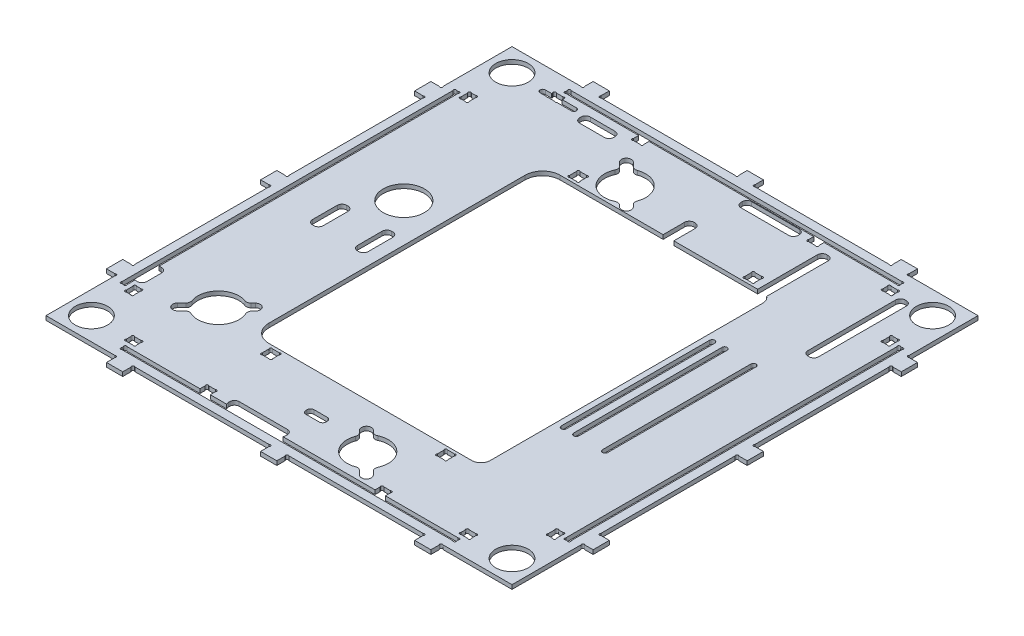
SolidWorks part; units mm, degrees
ref_plane "Front Plane" through (0, 0, 0) normal (0, 0, 1) x (1, 0, 0)
ref_plane "Top Plane" through (0, 0, 0) normal (0, 1, 0) x (1, 0, 0)
ref_plane "Right Plane" through (0, 0, 0) normal (1, 0, 0) x (0, 0, -1)
sketch "Sketch3" plane through (0, 0, 0) normal (0, 1, 0) x (1, 0, 0)
  line L0 (24.2967, 388.9163) -> (24.2967, 184.8114)
  line L1 (25.4192, 183.6889) -> (26.3491, 183.6889)
  line L2 (27.4717, 184.8114) -> (27.4717, 388.9163)
  line L3 (26.3491, 390.0389) -> (25.4192, 390.0389)
  line L4 (301.1033, 388.9163) -> (301.1033, 184.8114)
  line L5 (299.9808, 183.6889) -> (299.0509, 183.6889)
  line L6 (297.9283, 184.8114) -> (297.9283, 388.9163)
  line L7 (299.0509, 390.0389) -> (299.9808, 390.0389)
  line L8 (110.7905, 188.9529) -> (106.6855, 188.9529)
  line L9 (105.563, 190.0754) -> (105.563, 194.1803)
  line L10 (106.6855, 195.3029) -> (110.7905, 195.3029)
  line L11 (111.913, 194.1803) -> (111.913, 190.0754)
  line L12 (264.7525, 151.6355) -> (219.863, 151.6355)
  line L13 (219.863, 151.6355) -> (219.863, 154.8103)
  line L14 (218.7405, 155.9329) -> (214.6355, 155.9329)
  line L15 (213.513, 154.8103) -> (213.513, 151.6355)
  line L16 (213.513, 151.6355) -> (111.913, 151.6355)
  line L17 (111.913, 151.6355) -> (111.913, 154.8103)
  line L18 (110.7905, 155.9329) -> (106.6855, 155.9329)
  line L19 (105.563, 154.8103) -> (105.563, 151.6355)
  line L20 (105.563, 151.6355) -> (60.6475, 151.6355)
  line L21 (59.525, 150.513) -> (59.525, 149.5831)
  line L22 (60.6475, 148.4605) -> (264.7525, 148.4605)
  line L23 (265.875, 149.5831) -> (265.875, 150.513)
  line L24 (218.7405, 188.9529) -> (214.6355, 188.9529)
  line L25 (213.513, 190.0754) -> (213.513, 194.1803)
  line L26 (214.6355, 195.3029) -> (218.7405, 195.3029)
  line L27 (219.863, 194.1803) -> (219.863, 190.0754)
  line L28 (30.1368, 181.6364) -> (30.1368, 185.7413)
  line L29 (31.2593, 186.8639) -> (34.0143, 186.8639)
  line L30 (35.1368, 185.7413) -> (35.1368, 181.6364)
  line L31 (34.0143, 180.5139) -> (31.2593, 180.5139)
  line L32 (269.05, 158.1781) -> (269.05, 155.4232)
  line L33 (267.9275, 154.3007) -> (263.8225, 154.3007)
  line L34 (262.7, 155.4232) -> (262.7, 158.1781)
  line L35 (263.8225, 159.3007) -> (267.9275, 159.3007)
  line L36 (290.2632, 181.6364) -> (290.2632, 185.7413)
  line L37 (291.3857, 186.8639) -> (294.1407, 186.8639)
  line L38 (295.2632, 185.7413) -> (295.2632, 181.6364)
  line L39 (294.1407, 180.5139) -> (291.3857, 180.5139)
  line L40 (56.35, 158.1781) -> (56.35, 155.4232)
  line L41 (57.4725, 154.3007) -> (61.5775, 154.3007)
  line L42 (62.7, 155.4232) -> (62.7, 158.1781)
  line L43 (61.5775, 159.3007) -> (57.4725, 159.3007)
  line L44 (110.7905, 384.7749) -> (106.6855, 384.7749)
  line L45 (105.563, 383.6523) -> (105.563, 379.5474)
  line L46 (106.6855, 378.4249) -> (110.7905, 378.4249)
  line L47 (111.913, 379.5474) -> (111.913, 383.6523)
  line L48 (264.7525, 422.0922) -> (219.863, 422.0922)
  line L49 (219.863, 422.0922) -> (219.863, 418.9174)
  line L50 (218.7405, 417.7949) -> (214.6355, 417.7949)
  line L51 (213.513, 418.9174) -> (213.513, 422.0922)
  line L52 (213.513, 422.0922) -> (111.913, 422.0922)
  line L53 (111.913, 422.0922) -> (111.913, 418.9174)
  line L54 (110.7905, 417.7949) -> (106.6855, 417.7949)
  line L55 (105.563, 418.9174) -> (105.563, 422.0922)
  line L56 (105.563, 422.0922) -> (60.6475, 422.0922)
  line L57 (59.525, 423.2147) -> (59.525, 424.1447)
  line L58 (60.6475, 425.2672) -> (264.7525, 425.2672)
  line L59 (265.875, 424.1447) -> (265.875, 423.2147)
  line L60 (218.7405, 384.7749) -> (214.6355, 384.7749)
  line L61 (213.513, 383.6523) -> (213.513, 379.5474)
  line L62 (214.6355, 378.4249) -> (218.7405, 378.4249)
  line L63 (219.863, 379.5474) -> (219.863, 383.6523)
  line L64 (30.1368, 392.0913) -> (30.1368, 387.9864)
  line L65 (31.2593, 386.8639) -> (34.0143, 386.8639)
  line L66 (35.1368, 387.9864) -> (35.1368, 392.0913)
  line L67 (34.0143, 393.2139) -> (31.2593, 393.2139)
  line L68 (269.05, 415.5496) -> (269.05, 418.3045)
  line L69 (267.9275, 419.4271) -> (263.8225, 419.4271)
  line L70 (262.7, 418.3045) -> (262.7, 415.5496)
  line L71 (263.8225, 414.4271) -> (267.9275, 414.4271)
  line L72 (290.2632, 392.0913) -> (290.2632, 387.9864)
  line L73 (291.3857, 386.8639) -> (294.1407, 386.8639)
  line L74 (295.2632, 387.9864) -> (295.2632, 392.0913)
  line L75 (294.1407, 393.2139) -> (291.3857, 393.2139)
  line L76 (56.35, 415.5496) -> (56.35, 418.3045)
  line L77 (57.4725, 419.4271) -> (61.5775, 419.4271)
  line L78 (62.7, 418.3045) -> (62.7, 415.5496)
  line L79 (61.5775, 414.4271) -> (57.4725, 414.4271)
  line L80 (306.35, 430.5139) -> (306.35, 387.9864)
  line L81 (307.4725, 386.8639) -> (312.7, 386.8639)
  line L82 (312.7, 386.8639) -> (312.7, 376.8639)
  line L83 (312.7, 376.8639) -> (307.4725, 376.8639)
  line L84 (306.35, 375.7413) -> (306.35, 292.9864)
  line L85 (307.4725, 291.8639) -> (312.7, 291.8639)
  line L86 (312.7, 291.8639) -> (312.7, 281.8639)
  line L87 (312.7, 281.8639) -> (307.4725, 281.8639)
  line L88 (306.35, 280.7413) -> (306.35, 197.9864)
  line L89 (307.4725, 196.8639) -> (312.7, 196.8639)
  line L90 (312.7, 196.8639) -> (312.7, 186.8639)
  line L91 (312.7, 186.8639) -> (307.4725, 186.8639)
  line L92 (306.35, 185.7413) -> (306.35, 143.2139)
  line L93 (306.35, 143.2139) -> (263.8225, 143.2139)
  line L94 (262.7, 142.0913) -> (262.7, 136.8639)
  line L95 (262.7, 136.8639) -> (252.7, 136.8639)
  line L96 (252.7, 136.8639) -> (252.7, 142.0913)
  line L97 (251.5775, 143.2139) -> (168.7969, 143.2139)
  line L98 (167.7, 142.0668) -> (167.7, 136.8639)
  line L99 (167.7, 136.8639) -> (157.7, 136.8639)
  line L100 (157.7, 136.8639) -> (157.7, 142.0668)
  line L101 (156.6031, 143.2139) -> (73.7969, 143.2139)
  line L102 (72.7, 142.0668) -> (72.7, 136.8639)
  line L103 (72.7, 136.8639) -> (62.7, 136.8639)
  line L104 (62.7, 136.8639) -> (62.7, 142.0668)
  line L105 (61.6031, 143.2139) -> (19.05, 143.2139)
  line L106 (19.05, 143.2139) -> (19.05, 185.7413)
  line L107 (17.9275, 186.8639) -> (12.7, 186.8639)
  line L108 (12.7, 186.8639) -> (12.7, 196.8639)
  line L109 (12.7, 196.8639) -> (17.9275, 196.8639)
  line L110 (19.05, 197.9864) -> (19.05, 280.7413)
  line L111 (17.9275, 281.8639) -> (12.7, 281.8639)
  line L112 (12.7, 281.8639) -> (12.7, 291.8639)
  line L113 (12.7, 291.8639) -> (17.9275, 291.8639)
  line L114 (19.05, 292.9864) -> (19.05, 375.7413)
  line L115 (17.8823, 376.8148) -> (12.7, 376.8148)
  line L116 (12.7, 376.8148) -> (12.7, 386.8639)
  line L117 (12.7, 386.8639) -> (17.9275, 386.8639)
  line L118 (19.05, 387.9864) -> (19.05, 430.5139)
  line L119 (19.05, 430.5139) -> (61.6031, 430.5139)
  line L120 (62.7, 431.6609) -> (62.7, 436.8639)
  line L121 (62.7, 436.8639) -> (72.7, 436.8639)
  line L122 (72.7, 436.8639) -> (72.7, 431.6609)
  line L123 (73.7969, 430.5139) -> (156.6031, 430.5139)
  line L124 (157.7, 431.6609) -> (157.7, 436.8639)
  line L125 (157.7, 436.8639) -> (167.7, 436.8639)
  line L126 (167.7, 436.8639) -> (167.7, 431.6609)
  line L127 (168.7969, 430.5139) -> (251.5775, 430.5139)
  line L128 (252.7, 431.6364) -> (252.7, 436.8148)
  line L129 (252.7, 436.8148) -> (262.7, 436.8639)
  line L130 (262.7, 436.8639) -> (262.7, 431.6364)
  line L131 (263.8225, 430.5139) -> (306.35, 430.5139)
  line L132 (120.6384, 403.7302) -> (118.1286, 406.2398)
  line L133 (113.8862, 401.9969) -> (116.0645, 399.8188)
  line L134 (136.8964, 378.9889) -> (137.8765, 378.0089)
  line L135 (142.1189, 382.2518) -> (140.8074, 383.5632)
  line L136 (55.3635, 193.0636) -> (52.8425, 190.5653)
  line L137 (57.0659, 186.3035) -> (59.2539, 188.4719)
  line L138 (80.1789, 209.2084) -> (81.1633, 210.1839)
  line L139 (76.9399, 214.4457) -> (75.6225, 213.1402)
  line L140 (198.3429, 157.2294) -> (200.8527, 154.7198)
  line L141 (205.0951, 158.9627) -> (202.9168, 161.1408)
  line L142 (182.0849, 181.9708) -> (181.1048, 182.9507)
  line L143 (176.8624, 178.7079) -> (178.1739, 177.3965)
  line L144 (171.8479, 376.6786) -> (102.563, 376.6786)
  line L145 (91.7693, 365.8848) -> (91.7693, 207.8849)
  line L146 (102.563, 197.0911) -> (227.563, 197.0911)
  line L147 (233.3568, 202.8849) -> (233.3568, 370.8848)
  line L148 (227.563, 376.6786) -> (171.8479, 376.6786)
  line L149 (26.6779, 203.6185) -> (26.6779, 189.946)
  line L150 (26.6779, 189.946) -> (27.1874, 189.7506)
  line L151 (28.2194, 189.5594) -> (29.0444, 189.5594)
  line L152 (31.9256, 192.4406) -> (31.9256, 201.6695)
  line L153 (29.0444, 204.5508) -> (28.2194, 204.5508)
  line L154 (27.1874, 204.3596) -> (26.6779, 203.6185)
  line L155 (71.648, 414.491) -> (52.4164, 414.491)
  line L156 (52.4164, 417.666) -> (71.648, 417.666)
  line L157 (96.0105, 410.4668) -> (80.7705, 410.4668)
  line L158 (77.8892, 413.348) -> (77.8892, 414.173)
  line L159 (80.7705, 417.0543) -> (96.0105, 417.0543)
  line L160 (98.8917, 414.173) -> (98.8917, 413.348)
  line L161 (77.5933, 276.6911) -> (77.5933, 291.9311)
  line L162 (80.4745, 294.8124) -> (81.2995, 294.8124)
  line L163 (84.1808, 291.9311) -> (84.1808, 276.6911)
  line L164 (81.2995, 273.8099) -> (80.4745, 273.8099)
  line L165 (49.9033, 276.6911) -> (49.9033, 291.9311)
  line L166 (52.7845, 294.8124) -> (53.6095, 294.8124)
  line L167 (56.4908, 291.9311) -> (56.4908, 276.6911)
  line L168 (53.6095, 273.8099) -> (52.7845, 273.8099)
  line L169 (156.1589, 151.0537) -> (122.5045, 151.0537)
  line L170 (121.5831, 153.1656) -> (121.5831, 153.9906)
  line L171 (124.4644, 156.8719) -> (154.199, 156.8719)
  line L172 (157.0802, 153.9906) -> (157.0802, 153.1656)
  line L173 (239.9218, 334.6547) -> (239.9218, 243.2147)
  line L174 (236.7468, 243.2147) -> (236.7468, 334.6547)
  line L175 (247.5418, 334.6547) -> (247.5418, 243.2147)
  line L176 (244.3668, 243.2147) -> (244.3668, 334.6547)
  line L177 (265.3218, 334.6547) -> (265.3218, 243.2147)
  line L178 (262.1468, 243.2147) -> (262.1468, 334.6547)
  line L179 (275.4782, 416.4269) -> (276.3032, 416.4269)
  line L180 (279.1844, 413.5456) -> (279.1844, 359.3806)
  line L181 (276.3032, 356.4994) -> (275.4782, 356.4994)
  line L182 (272.5969, 359.3806) -> (272.5969, 413.5456)
  line L183 (205.1477, 415.0213) -> (175.6917, 415.0213)
  line L184 (172.8104, 417.9025) -> (172.8104, 418.7275)
  line L185 (175.6917, 421.6088) -> (205.1477, 421.6088)
  line L186 (208.0289, 418.7275) -> (208.0289, 417.9025)
  line L187 (224.3369, 375.0911) -> (227.563, 375.0911)
  line L188 (229.7231, 374.4941) -> (230.9244, 373.7751)
  line L189 (230.9244, 373.7751) -> (230.9244, 413.5456)
  line L190 (228.0432, 416.4269) -> (227.2182, 416.4269)
  line L191 (224.3369, 413.5456) -> (224.3369, 375.0911)
  line L192 (166.0541, 389.9116) -> (166.0541, 375.0911)
  line L193 (166.0541, 375.0911) -> (172.6416, 375.0911)
  line L194 (172.6416, 375.0911) -> (172.6416, 389.9116)
  line L195 (169.7604, 392.7929) -> (168.9354, 392.7929)
  line L196 (151.846, 175.6361) -> (160.041, 175.6361)
  line L197 (162.1285, 173.5486) -> (162.1285, 172.7236)
  line L198 (160.041, 170.6361) -> (151.846, 170.6361)
  line L199 (149.7585, 172.7236) -> (149.7585, 173.5486)
  arc A0 (24.2967, 184.8114) -> (25.4192, 183.6889) centre (24.8579, 184.2501) ccw
  arc A1 (26.3491, 183.6889) -> (27.4717, 184.8114) centre (26.9104, 184.2501) ccw
  arc A2 (27.4717, 388.9163) -> (26.3491, 390.0389) centre (26.9104, 389.4776) ccw
  arc A3 (25.4192, 390.0389) -> (24.2967, 388.9163) centre (24.8579, 389.4776) ccw
  arc A4 (299.9808, 183.6889) -> (301.1033, 184.8114) centre (300.5421, 184.2501) ccw
  arc A5 (297.9283, 184.8114) -> (299.0509, 183.6889) centre (298.4896, 184.2501) ccw
  arc A6 (299.0509, 390.0389) -> (297.9283, 388.9163) centre (298.4896, 389.4776) ccw
  arc A7 (301.1033, 388.9163) -> (299.9808, 390.0389) centre (300.5421, 389.4776) ccw
  arc A8 (105.563, 190.0754) -> (106.6855, 188.9529) centre (106.1243, 189.5141) ccw
  arc A9 (106.6855, 195.3029) -> (105.563, 194.1803) centre (106.1243, 194.7416) ccw
  arc A10 (111.913, 194.1803) -> (110.7905, 195.3029) centre (111.3517, 194.7416) ccw
  arc A11 (110.7905, 188.9529) -> (111.913, 190.0754) centre (111.3517, 189.5141) ccw
  arc A12 (265.875, 150.513) -> (264.7525, 151.6355) centre (265.3137, 151.0743) ccw
  arc A13 (219.863, 154.8103) -> (218.7405, 155.9329) centre (219.3017, 155.3716) ccw
  arc A14 (214.6355, 155.9329) -> (213.513, 154.8103) centre (214.0743, 155.3716) ccw
  arc A15 (111.913, 154.8103) -> (110.7905, 155.9329) centre (111.3517, 155.3716) ccw
  arc A16 (106.6855, 155.9329) -> (105.563, 154.8103) centre (106.1243, 155.3716) ccw
  arc A17 (60.6475, 151.6355) -> (59.525, 150.513) centre (60.0863, 151.0743) ccw
  arc A18 (59.525, 149.5831) -> (60.6475, 148.4605) centre (60.0863, 149.0218) ccw
  arc A19 (264.7525, 148.4605) -> (265.875, 149.5831) centre (265.3137, 149.0218) ccw
  arc A20 (213.513, 190.0754) -> (214.6355, 188.9529) centre (214.0743, 189.5141) ccw
  arc A21 (214.6355, 195.3029) -> (213.513, 194.1803) centre (214.0743, 194.7416) ccw
  arc A22 (219.863, 194.1803) -> (218.7405, 195.3029) centre (219.3017, 194.7416) ccw
  arc A23 (218.7405, 188.9529) -> (219.863, 190.0754) centre (219.3017, 189.5141) ccw
  arc A24 (31.2593, 186.8639) -> (30.1368, 185.7413) centre (30.6981, 186.3026) ccw
  arc A25 (35.1368, 185.7413) -> (34.0143, 186.8639) centre (34.5755, 186.3026) ccw
  arc A26 (34.0143, 180.5139) -> (35.1368, 181.6364) centre (34.5755, 181.0751) ccw
  arc A27 (30.1368, 181.6364) -> (31.2593, 180.5139) centre (30.6981, 181.0751) ccw
  arc A28 (267.9275, 154.3007) -> (269.05, 155.4232) centre (268.4887, 154.8619) ccw
  arc A29 (262.7, 155.4232) -> (263.8225, 154.3007) centre (263.2613, 154.8619) ccw
  arc A30 (263.8225, 159.3007) -> (262.7, 158.1781) centre (263.2613, 158.7394) ccw
  arc A31 (269.05, 158.1781) -> (267.9275, 159.3007) centre (268.4887, 158.7394) ccw
  arc A32 (291.3857, 186.8639) -> (290.2632, 185.7413) centre (290.8245, 186.3026) ccw
  arc A33 (295.2632, 185.7413) -> (294.1407, 186.8639) centre (294.7019, 186.3026) ccw
  arc A34 (294.1407, 180.5139) -> (295.2632, 181.6364) centre (294.7019, 181.0751) ccw
  arc A35 (290.2632, 181.6364) -> (291.3857, 180.5139) centre (290.8245, 181.0751) ccw
  arc A36 (56.35, 155.4232) -> (57.4725, 154.3007) centre (56.9113, 154.8619) ccw
  arc A37 (61.5775, 154.3007) -> (62.7, 155.4232) centre (62.1387, 154.8619) ccw
  arc A38 (62.7, 158.1781) -> (61.5775, 159.3007) centre (62.1387, 158.7394) ccw
  arc A39 (57.4725, 159.3007) -> (56.35, 158.1781) centre (56.9113, 158.7394) ccw
  arc A40 (106.6855, 384.7749) -> (105.563, 383.6523) centre (106.1243, 384.2136) ccw
  arc A41 (105.563, 379.5474) -> (106.6855, 378.4249) centre (106.1243, 378.9861) ccw
  arc A42 (110.7905, 378.4249) -> (111.913, 379.5474) centre (111.3517, 378.9861) ccw
  arc A43 (111.913, 383.6523) -> (110.7905, 384.7749) centre (111.3517, 384.2136) ccw
  arc A44 (264.7525, 422.0922) -> (265.875, 423.2147) centre (265.3137, 422.6535) ccw
  arc A45 (218.7405, 417.7949) -> (219.863, 418.9174) centre (219.3017, 418.3561) ccw
  arc A46 (213.513, 418.9174) -> (214.6355, 417.7949) centre (214.0743, 418.3561) ccw
  arc A47 (110.7905, 417.7949) -> (111.913, 418.9174) centre (111.3517, 418.3561) ccw
  arc A48 (105.563, 418.9174) -> (106.6855, 417.7949) centre (106.1243, 418.3561) ccw
  arc A49 (59.525, 423.2147) -> (60.6475, 422.0922) centre (60.0863, 422.6535) ccw
  arc A50 (60.6475, 425.2672) -> (59.525, 424.1447) centre (60.0863, 424.7059) ccw
  arc A51 (265.875, 424.1447) -> (264.7525, 425.2672) centre (265.3137, 424.7059) ccw
  arc A52 (214.6355, 384.7749) -> (213.513, 383.6523) centre (214.0743, 384.2136) ccw
  arc A53 (213.513, 379.5474) -> (214.6355, 378.4249) centre (214.0743, 378.9861) ccw
  arc A54 (218.7405, 378.4249) -> (219.863, 379.5474) centre (219.3017, 378.9861) ccw
  arc A55 (219.863, 383.6523) -> (218.7405, 384.7749) centre (219.3017, 384.2136) ccw
  arc A56 (30.1368, 387.9864) -> (31.2593, 386.8639) centre (30.6981, 387.4251) ccw
  arc A57 (34.0143, 386.8639) -> (35.1368, 387.9864) centre (34.5755, 387.4251) ccw
  arc A58 (35.1368, 392.0913) -> (34.0143, 393.2139) centre (34.5755, 392.6526) ccw
  arc A59 (31.2593, 393.2139) -> (30.1368, 392.0913) centre (30.6981, 392.6526) ccw
  arc A60 (269.05, 418.3045) -> (267.9275, 419.4271) centre (268.4887, 418.8658) ccw
  arc A61 (263.8225, 419.4271) -> (262.7, 418.3045) centre (263.2613, 418.8658) ccw
  arc A62 (262.7, 415.5496) -> (263.8225, 414.4271) centre (263.2613, 414.9883) ccw
  arc A63 (267.9275, 414.4271) -> (269.05, 415.5496) centre (268.4887, 414.9883) ccw
  arc A64 (290.2632, 387.9864) -> (291.3857, 386.8639) centre (290.8245, 387.4251) ccw
  arc A65 (294.1407, 386.8639) -> (295.2632, 387.9864) centre (294.7019, 387.4251) ccw
  arc A66 (295.2632, 392.0913) -> (294.1407, 393.2139) centre (294.7019, 392.6526) ccw
  arc A67 (291.3857, 393.2139) -> (290.2632, 392.0913) centre (290.8245, 392.6526) ccw
  arc A68 (57.4725, 419.4271) -> (56.35, 418.3045) centre (56.9113, 418.8658) ccw
  arc A69 (62.7, 418.3045) -> (61.5775, 419.4271) centre (62.1387, 418.8658) ccw
  arc A70 (61.5775, 414.4271) -> (62.7, 415.5496) centre (62.1387, 414.9883) ccw
  arc A71 (56.35, 415.5496) -> (57.4725, 414.4271) centre (56.9113, 414.9883) ccw
  arc A72 (306.35, 387.9864) -> (307.4725, 386.8639) centre (306.9113, 387.4251) ccw
  arc A73 (307.4725, 376.8639) -> (306.35, 375.7413) centre (306.9113, 376.3026) ccw
  arc A74 (306.35, 292.9864) -> (307.4725, 291.8639) centre (306.9113, 292.4251) ccw
  arc A75 (307.4725, 281.8639) -> (306.35, 280.7413) centre (306.9113, 281.3026) ccw
  arc A76 (306.35, 197.9864) -> (307.4725, 196.8639) centre (306.9113, 197.4251) ccw
  arc A77 (307.4725, 186.8639) -> (306.35, 185.7413) centre (306.9113, 186.3026) ccw
  arc A78 (263.8225, 143.2139) -> (262.7, 142.0913) centre (263.2613, 142.6526) ccw
  arc A79 (252.7, 142.0913) -> (251.5775, 143.2139) centre (252.1387, 142.6526) ccw
  arc A80 (168.7969, 143.2139) -> (167.7, 142.0668) centre (168.2613, 142.628) ccw
  arc A81 (157.7, 142.0668) -> (156.6031, 143.2139) centre (157.1387, 142.628) ccw
  arc A82 (73.7969, 143.2139) -> (72.7, 142.0668) centre (73.2613, 142.628) ccw
  arc A83 (62.7, 142.0668) -> (61.6031, 143.2139) centre (62.1387, 142.628) ccw
  arc A84 (19.05, 185.7413) -> (17.9275, 186.8639) centre (18.4887, 186.3026) ccw
  arc A85 (17.9275, 196.8639) -> (19.05, 197.9864) centre (18.4887, 197.4251) ccw
  arc A86 (19.05, 280.7413) -> (17.9275, 281.8639) centre (18.4887, 281.3026) ccw
  arc A87 (17.9275, 291.8639) -> (19.05, 292.9864) centre (18.4887, 292.4251) ccw
  arc A88 (19.05, 375.7413) -> (17.8823, 376.8148) centre (18.4887, 376.3026) ccw
  arc A89 (17.9275, 386.8639) -> (19.05, 387.9864) centre (18.4887, 387.4251) ccw
  arc A90 (61.6031, 430.5139) -> (62.7, 431.6609) centre (62.1387, 431.0997) ccw
  arc A91 (72.7, 431.6609) -> (73.7969, 430.5139) centre (73.2613, 431.0997) ccw
  arc A92 (156.6031, 430.5139) -> (157.7, 431.6609) centre (157.1387, 431.0997) ccw
  arc A93 (167.7, 431.6609) -> (168.7969, 430.5139) centre (168.2613, 431.0997) ccw
  arc A94 (251.5775, 430.5139) -> (252.7, 431.6364) centre (252.1387, 431.0751) ccw
  arc A95 (262.7, 431.6364) -> (263.8225, 430.5139) centre (263.2613, 431.0751) ccw
  circle A96 centre (68.0019, 314.8681) radius 12.7
  circle A97 centre (33.05, 157.2139) radius 10
  circle A98 centre (33.05, 416.5139) radius 10
  circle A99 centre (292.35, 157.2139) radius 10
  circle A100 centre (292.35, 416.5139) radius 10
  arc A101 (140.1145, 386.7241) -> (140.8074, 383.5632) centre (142.9286, 385.6846) ccw
  arc A102 (140.1145, 386.7241) -> (123.7994, 403.0376) centre (128.2013, 391.1249) ccw
  arc A103 (120.6384, 403.7302) -> (123.7994, 403.0376) centre (122.7596, 405.8516) ccw
  arc A104 (118.1286, 406.2398) -> (113.8862, 401.9969) centre (116.0074, 404.1184) ccw
  arc A105 (116.6677, 396.4415) -> (116.0645, 399.8188) centre (113.9433, 397.6974) ccw
  arc A106 (116.6677, 396.4415) -> (133.519, 379.5918) centre (128.2013, 391.1249) ccw
  arc A107 (136.8964, 378.9889) -> (133.519, 379.5918) centre (134.7752, 376.8674) ccw
  arc A108 (137.8765, 378.0089) -> (142.1189, 382.2518) centre (139.9977, 380.1303) ccw
  arc A109 (72.4584, 212.4617) -> (75.6225, 213.1402) centre (73.5108, 215.2711) ccw
  arc A110 (72.4584, 212.4617) -> (56.0705, 196.2215) centre (68.0033, 200.5688) ccw
  arc A111 (55.3635, 193.0636) -> (56.0705, 196.2215) centre (53.2518, 195.1945) ccw
  arc A112 (52.8425, 190.5653) -> (57.0659, 186.3035) centre (54.9542, 188.4344) ccw
  arc A113 (62.6339, 189.0597) -> (59.2539, 188.4719) centre (61.3656, 186.341) ccw
  arc A114 (62.6339, 189.0597) -> (79.5605, 205.8338) centre (68.0033, 200.5688) ccw
  arc A115 (80.1789, 209.2084) -> (79.5605, 205.8338) centre (82.2906, 207.0775) ccw
  arc A116 (81.1633, 210.1839) -> (76.9399, 214.4457) centre (79.0516, 212.3148) ccw
  arc A117 (178.8668, 174.2355) -> (178.1739, 177.3965) centre (176.0527, 175.275) ccw
  arc A118 (178.8668, 174.2355) -> (195.1819, 157.922) centre (190.78, 169.8348) ccw
  arc A119 (198.3429, 157.2294) -> (195.1819, 157.922) centre (196.2217, 155.108) ccw
  arc A120 (200.8527, 154.7198) -> (205.0951, 158.9627) centre (202.9739, 156.8413) ccw
  arc A121 (202.3136, 164.5181) -> (202.9168, 161.1408) centre (205.038, 163.2622) ccw
  arc A122 (202.3136, 164.5181) -> (185.4622, 181.3678) centre (190.78, 169.8348) ccw
  arc A123 (182.0849, 181.9708) -> (185.4622, 181.3678) centre (184.2061, 184.0922) ccw
  arc A124 (181.1048, 182.9507) -> (176.8624, 178.7079) centre (178.9836, 180.8293) ccw
  arc A125 (102.563, 376.6786) -> (91.7693, 365.8848) centre (102.563, 365.8848) ccw
  arc A126 (91.7693, 207.8849) -> (102.563, 197.0911) centre (102.563, 207.8849) ccw
  arc A127 (227.563, 197.0911) -> (233.3568, 202.8849) centre (227.563, 202.8849) ccw
  arc A128 (233.3568, 370.8848) -> (227.563, 376.6786) centre (227.563, 370.8848) ccw
  arc A129 (27.1874, 189.7506) -> (28.2194, 189.5594) centre (28.2194, 192.4406) ccw
  arc A130 (29.0444, 189.5594) -> (31.9256, 192.4406) centre (29.0444, 192.4406) ccw
  arc A131 (31.9256, 201.6695) -> (29.0444, 204.5508) centre (29.0444, 201.6695) ccw
  arc A132 (28.2194, 204.5508) -> (27.1874, 204.3596) centre (28.2194, 201.6695) ccw
  arc A133 (52.4164, 417.666) -> (52.4164, 414.491) centre (52.4164, 416.0785) ccw
  arc A134 (71.648, 414.491) -> (71.648, 417.666) centre (71.648, 416.0785) ccw
  arc A135 (77.8892, 413.348) -> (80.7705, 410.4668) centre (80.7705, 413.348) ccw
  arc A136 (80.7705, 417.0543) -> (77.8892, 414.173) centre (80.7705, 414.173) ccw
  arc A137 (98.8917, 414.173) -> (96.0105, 417.0543) centre (96.0105, 414.173) ccw
  arc A138 (96.0105, 410.4668) -> (98.8917, 413.348) centre (96.0105, 413.348) ccw
  arc A139 (80.4745, 294.8124) -> (77.5933, 291.9311) centre (80.4745, 291.9311) ccw
  arc A140 (84.1808, 291.9311) -> (81.2995, 294.8124) centre (81.2995, 291.9311) ccw
  arc A141 (81.2995, 273.8099) -> (84.1808, 276.6911) centre (81.2995, 276.6911) ccw
  arc A142 (77.5933, 276.6911) -> (80.4745, 273.8099) centre (80.4745, 276.6911) ccw
  arc A143 (52.7845, 294.8124) -> (49.9033, 291.9311) centre (52.7845, 291.9311) ccw
  arc A144 (56.4908, 291.9311) -> (53.6095, 294.8124) centre (53.6095, 291.9311) ccw
  arc A145 (53.6095, 273.8099) -> (56.4908, 276.6911) centre (53.6095, 276.6911) ccw
  arc A146 (49.9033, 276.6911) -> (52.7845, 273.8099) centre (52.7845, 276.6911) ccw
  arc A147 (156.1589, 151.0537) -> (157.0802, 153.1656) centre (154.199, 153.1656) ccw
  arc A148 (121.5831, 153.1656) -> (122.5045, 151.0537) centre (124.4644, 153.1656) ccw
  arc A149 (124.4644, 156.8719) -> (121.5831, 153.9906) centre (124.4644, 153.9906) ccw
  arc A150 (157.0802, 153.9906) -> (154.199, 156.8719) centre (154.199, 153.9906) ccw
  arc A151 (236.7468, 243.2147) -> (239.9218, 243.2147) centre (238.3343, 243.2147) ccw
  arc A152 (239.9218, 334.6547) -> (236.7468, 334.6547) centre (238.3343, 334.6547) ccw
  arc A153 (244.3668, 243.2147) -> (247.5418, 243.2147) centre (245.9543, 243.2147) ccw
  arc A154 (247.5418, 334.6547) -> (244.3668, 334.6547) centre (245.9543, 334.6547) ccw
  arc A155 (262.1468, 243.2147) -> (265.3218, 243.2147) centre (263.7343, 243.2147) ccw
  arc A156 (265.3218, 334.6547) -> (262.1468, 334.6547) centre (263.7343, 334.6547) ccw
  arc A157 (279.1844, 413.5456) -> (276.3032, 416.4269) centre (276.3032, 413.5456) ccw
  arc A158 (276.3032, 356.4994) -> (279.1844, 359.3806) centre (276.3032, 359.3806) ccw
  arc A159 (272.5969, 359.3806) -> (275.4782, 356.4994) centre (275.4782, 359.3806) ccw
  arc A160 (275.4782, 416.4269) -> (272.5969, 413.5456) centre (275.4782, 413.5456) ccw
  arc A161 (172.8104, 417.9025) -> (175.6917, 415.0213) centre (175.6917, 417.9025) ccw
  arc A162 (175.6917, 421.6088) -> (172.8104, 418.7275) centre (175.6917, 418.7275) ccw
  arc A163 (208.0289, 418.7275) -> (205.1477, 421.6088) centre (205.1477, 418.7275) ccw
  arc A164 (205.1477, 415.0213) -> (208.0289, 417.9025) centre (205.1477, 417.9025) ccw
  arc A165 (229.7231, 374.4941) -> (227.563, 375.0911) centre (227.563, 370.8848) ccw
  arc A166 (230.9244, 413.5456) -> (228.0432, 416.4269) centre (228.0432, 413.5456) ccw
  arc A167 (227.2182, 416.4269) -> (224.3369, 413.5456) centre (227.2182, 413.5456) ccw
  arc A168 (172.6416, 389.9116) -> (169.7604, 392.7929) centre (169.7604, 389.9116) ccw
  arc A169 (168.9354, 392.7929) -> (166.0541, 389.9116) centre (168.9354, 389.9116) ccw
  arc A170 (162.1285, 173.5486) -> (160.041, 175.6361) centre (160.041, 173.5486) ccw
  arc A171 (160.041, 170.6361) -> (162.1285, 172.7236) centre (160.041, 172.7236) ccw
  arc A172 (149.7585, 172.7236) -> (151.846, 170.6361) centre (151.846, 172.7236) ccw
  arc A173 (151.846, 175.6361) -> (149.7585, 173.5486) centre (151.846, 173.5486) ccw
extrude "Boss-Extrude1" add sketch "Sketch3" along normal blind 2.54 contours A95 L130 L129 L128 A94 L127 A93 L126 L125 L124 A92 L123 A91 L122 L121 L120 A90 L119 L118 A89 L117 L116 L115 A88 L114 A87 L113 L112 L111 A86 L110 A85 L109 L108 L107 A84 L106 L105 A83 L104 L103 L102 A82 L101 A81 L100 L99 L98 A80 L97 A79 region at (302.1074, 0, -409.2501)
